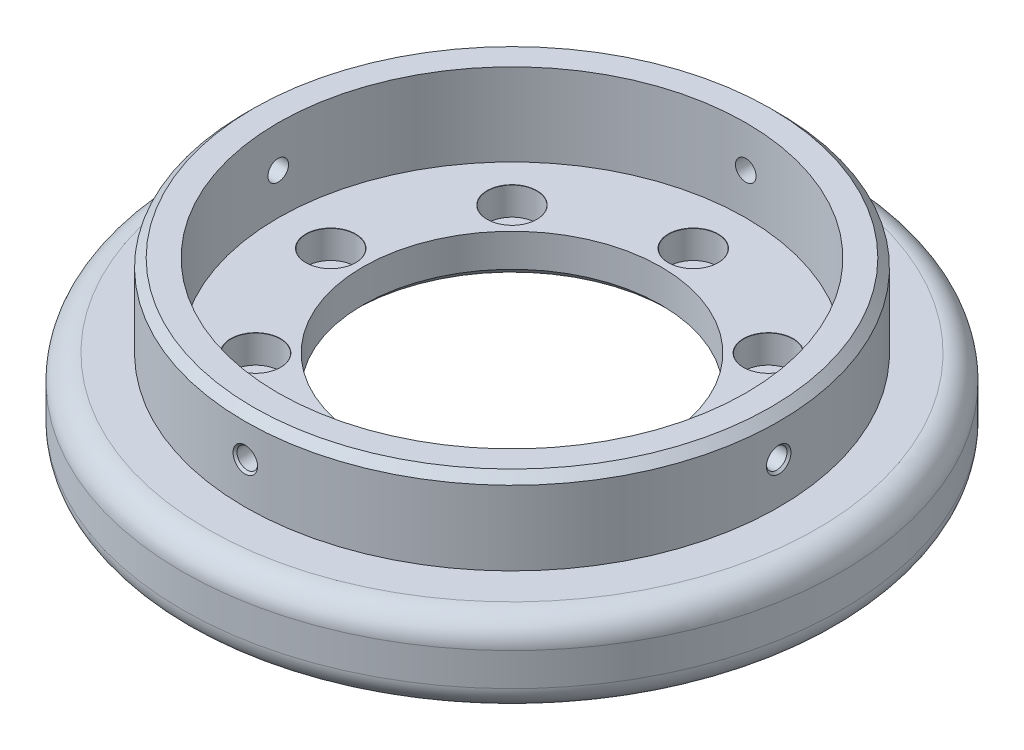
SolidWorks part; units mm, degrees
ref_plane "前视基准面" through (0, 0, 0) normal (0, 0, 1) x (1, 0, 0)
ref_plane "上视基准面" through (0, 0, 0) normal (0, 1, 0) x (1, 0, 0)
ref_plane "右视基准面" through (0, 0, 0) normal (1, 0, 0) x (0, 0, -1)
sketch "草图1" plane through (0, 0, 0) normal (0, 1, 0) x (1, 0, 0)
  circle A0 centre (0, 0) radius 40
  dimension "D1" = 80
extrude "凸台-拉伸1" add sketch "草图1" along normal blind 10
sketch "草图2" plane through (0, 0, 0) normal (0, -1, 0) x (1, 0, 0)
  circle A0 centre (0, 0) radius 27.25
  dimension "D1" = 54.5
extrude "切除-拉伸1" cut sketch "草图2" against normal offset from surface (5 mm away) 5 up to face at (0, 10, 40)
sketch "草图4" plane through (0, 10, 0) normal (0, 1, 0) x (1, 0, 0)
  circle A0 centre (0, 0) radius 32.4
  circle A1 centre (0, 0) radius 28.4
  dimension "D1" = 64.8
  dimension "D2" = 4
extrude "凸台-拉伸2" add sketch "草图4" along normal blind 10
sketch "草图5" plane through (0, 10, 0) normal (0, 1, 0) x (1, 0, 0)
  circle A0 centre (0, 0) radius 18.1
  dimension "D1" = 36.2
extrude "切除-拉伸2" cut sketch "草图5" against normal through all
sketch "草图6" plane through (0, 10, 0) normal (0, 1, 0) x (1, 0, 0)
  circle A0 centre (0, 0) radius 22 construction
  dimension "D1" = 44
hole_wizard "打孔尺寸(%根据)内六角圆柱头螺钉的类型3" positions "草图11" profile "草图12" counterbore size "M3" standard "GB" end condition through all
sketch "草图11" plane through (0, 10, 0) normal (0, 1, 0) x (1, 0, 0)
  circle A0 centre (0, 0) radius 22 construction
  point P0 (0, 22)
sketch "草图12" plane through (0, 10, -22) normal (1, 0, 0) x (0, 0, 1)
  line L0 (0, 0) -> (0, 10)
  line L1 (0, 10) -> (1.7, 10)
  line L3 (1.7, 10) -> (1.7, 3.4)
  line L4 (3, 3.4) -> (1.7, 3.4)
  line L5 (3, 3.4) -> (3, 0.025)
  line L6 (3, 0.025) -> (3.025, 0)
  line L7 (3.025, 0) -> (0, 0)
  line L8 (-3, 0.025) -> (-3.025, 0) construction
  line L11 (0, -6.35) -> (0, 107.95) construction
  dimension "通孔孔直径" = 3.4
  dimension "通孔孔深度" = 10
  dimension "柱形沉头孔直径" = 6
  dimension "柱形沉头孔深度" = 3.4
  dimension "近端锥形沉头孔直径" = 6.05
  dimension "近端锥形沉头孔角度" = 90
pattern_circular "阵列(圆周)1" count 8 over 360 about axis through (0, 10, 0) along (0, -1, 0) of "打孔尺寸(%根据)内六角圆柱头螺钉的类型3" reverse direction yes
ref_plane "基准面1" through (-32.4, 0, 0) normal (-1, 0, 0) x (0, 0, 1)
sketch "草图13" plane through (-32.4, 0, 0) normal (-1, 0, 0) x (0, 0, 1)
  line L0 (0, 20) -> (0, 15)
  line L1 (32.4, 20) -> (-32.4, 20) construction
  dimension "D1" = 5
hole_wizard "M3 螺纹孔1" positions "草图14" profile "草图16" tap size "M3" standard "GB" end condition up to next
sketch "草图14" plane through (-32.4, 0, 0) normal (-1, 0, 0) x (0, 0, 1)
  point P0 (0, 15)
sketch "草图16" plane through (-32.4, 15, 0) normal (0, 1, 0) x (0, 0, 1)
  line L0 (0, 0) -> (0, 4)
  line L1 (0, 4) -> (1.25, 4)
  line L2 (1.25, 4) -> (1.25, 0.275)
  line L3 (1.25, 0.275) -> (1.525, 0)
  line L5 (1.525, 0) -> (0, 0)
  line L6 (-1.25, 0.275) -> (-1.525, 0) construction
  line L11 (0, -6.35) -> (0, 107.95) construction
  dimension "通孔螺纹孔钻头直径" = 2.5
  dimension "通孔螺纹孔钻头深度" = 4
  dimension "近端锥形沉头孔直径" = 3.05
  dimension "近端锥形沉头孔角度" = 90
cosmetic thread "孔螺蚊线1" parameters "D2"=3
pattern_circular "阵列(圆周)2" count 4 over 360 about axis through (0, 20, 0) along (0, -1, 0) of "M3 螺纹孔1"
cosmetic thread "孔螺蚊线2" parameters "D2"=3
cosmetic thread "孔螺蚊线3" parameters "D2"=3
cosmetic thread "孔螺蚊线4" parameters "D2"=3
chamfer "倒角1" distance 1 angle 45 1 edges at (0, 20, 32.4)
chamfer "倒角2" distance 1 angle 45 1 edges at (0, 0, -27.25)
fillet "圆角1" radius 3 2 edges at (0, 0, 40) (0, 10, 40)
chamfer "倒角3" distance 1 angle 45 1 edges at (0, 5, 18.1)
equation "\"36。2\"=38"
